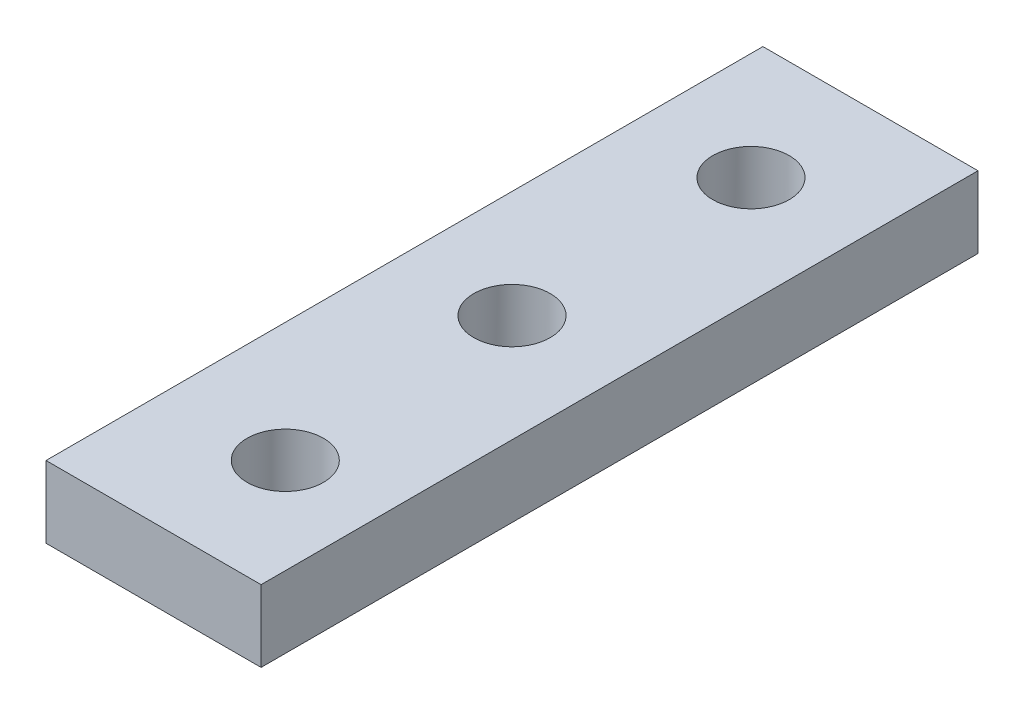
SolidWorks part; units mm, degrees
material "AISI 304"
ref_plane "Plan de face" through (0, 0, 0) normal (0, 0, 1) x (1, 0, 0)
ref_plane "Plan de dessus" through (0, 0, 0) normal (0, 1, 0) x (1, 0, 0)
ref_plane "Plan de droite" through (0, 0, 0) normal (1, 0, 0) x (0, 0, -1)
sketch "Esquisse1" plane through (0, 0, 0) normal (0, 0, 1) x (1, 0, 0)
  line L1 (0, 0) -> (9, 0)
  line L2 (0, 0) -> (0, 3)
  line L3 (0, 3) -> (9, 3)
  line L4 (9, 0) -> (9, 3)
  dimension "D1" = 3
  dimension "D2" = 9
extrude "Boss.-Extru.1" add sketch "Esquisse1" along normal blind 30
sketch "Esquisse4" plane through (0, 3, 0) normal (0, 1, 0) x (1, 0, 0)
  line L2 (4.5, -15) -> (4.5, -5) construction
  line L3 (9, -30) -> (9, 0) construction
  line L4 (0, -30) -> (0, 0) construction
  line L5 (0, -30) -> (0, 0) construction
  line L7 (9, 0) -> (0, 0) construction
  circle A0 centre (4.5, -5) radius 1.6
  circle A1 centre (4.5, -15) radius 1.6
  circle A2 centre (5, -24.9875) radius 1.6
  dimension "D1" = 3.2
  dimension "D2" = 3.2
  dimension "D5" = 3.2
  dimension "D3" = 10
  dimension "D4" = 5
  dimension "D6" = 10
  dimension "D7" = 5
extrude "Enlèv. mat.-Extru.1" cut sketch "Esquisse4" against normal through all
hole_wizard "Formsenkung für M2 Senkschraube mit Schlitz/Kreuzschlitz1" positions "Skizze1" profile "Skizze2" countersink size "M2" standard "ANSI Metrisch" end condition through all
sketch "Skizze1" plane through (0, 0, 0) normal (0, -1, 0) x (-1, 0, 0)
  point P0 (-4.5, -5)
  point P3 (-4.5, -15)
sketch "Skizze2" plane through (4.5, 0, 5) normal (1, 0, 0) x (0, 0, -1)
  line L0 (0, 0) -> (0, 3)
  line L1 (0, 3) -> (1.1, 3)
  line L2 (1.1, 3) -> (1.1, 1.1)
  line L3 (1.1, 1.1) -> (2.2, 0)
  line L5 (2.2, 0) -> (0, 0)
  line L6 (-1.1, 1.1) -> (-2.2, 0) construction
  line L11 (0, -6.35) -> (0, 107.95) construction
  dimension "Bohrerdurchmesser" = 2.2
  dimension "Bohrungstiefe" = 3
  dimension "Senkdurchmesser (Oben)" = 4.4
  dimension "Senkwinkel (Oben)" = 90
